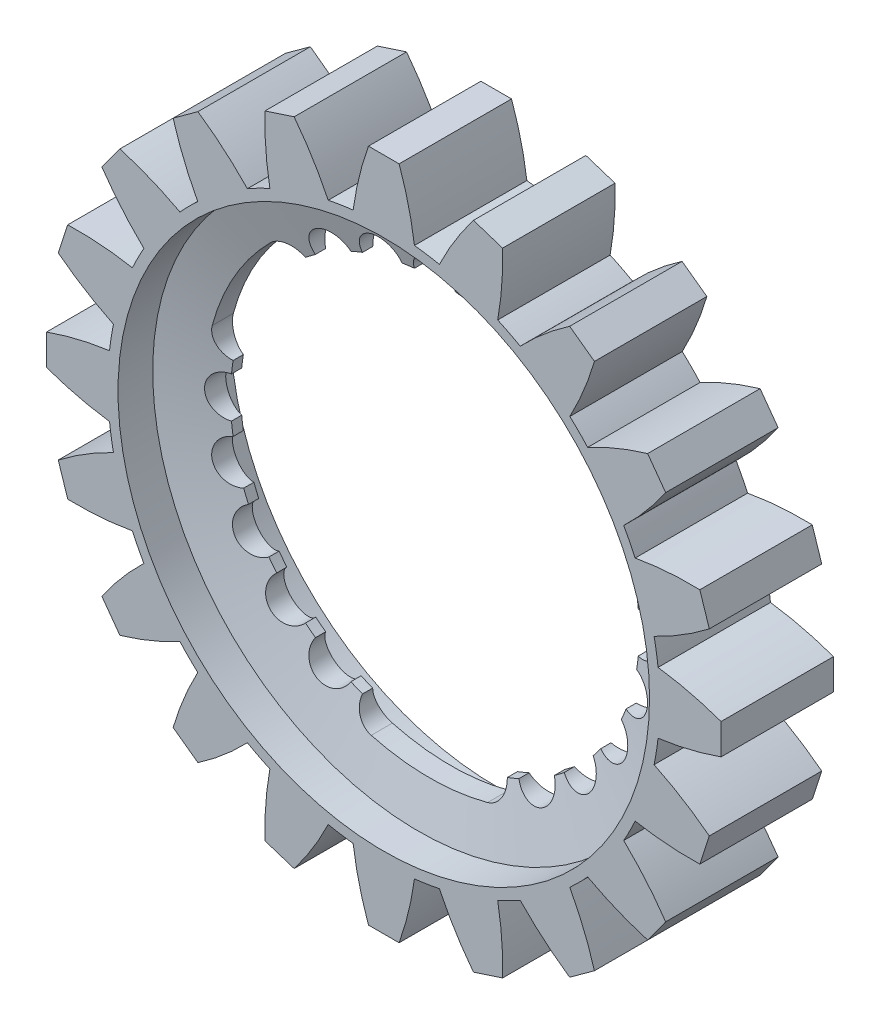
SolidWorks part; units mm, degrees
ref_plane "前视基准面" through (0, 0, 0) normal (0, 0, 1) x (1, 0, 0)
ref_plane "上视基准面" through (0, 0, 0) normal (0, 1, 0) x (1, 0, 0)
ref_plane "右视基准面" through (0, 0, 0) normal (1, 0, 0) x (0, 0, -1)
sketch "草图1" plane through (0, 0, 0) normal (0, 0, 1) x (1, 0, 0)
  circle A0 centre (0, 0) radius 13.5
extrude "凸台-拉伸1" add sketch "草图1" along normal blind 5.5
sketch "草图2" plane through (0, 0, 5.5) normal (0, 0, 1) x (1, 0, 0)
  circle A0 centre (0, 0) radius 10
extrude "切除-拉伸1" cut sketch "草图2" against normal through all
sketch "草图3" plane through (0, 0, 5.5) normal (0, 0, 1) x (1, 0, 0)
  circle A0 centre (0, 0) radius 13
extrude "切除-拉伸2" cut sketch "草图3" against normal blind 1.5
sketch "草图4" plane through (0, 0, 0) normal (0, 0, -1) x (-1, 0, 0)
  circle A0 centre (0, 0) radius 13
extrude "切除-拉伸3" cut sketch "草图4" against normal blind 1.5
chamfer "倒角1" distance 1 angle 75 2 edges at (-10, 0, 1.5) (10, 0, 4) first distance on face at (10, 0, 4)
sketch "草图5" plane through (0, 0, 5.5) normal (0, 0, 1) x (1, 0, 0)
  arc A0 (-1.6105, 9.8695) -> (-3.54, 9.3525) centre (0, 0) ccw
  arc A1 (-4.1101, 9.1163) -> (-5.8399, 8.1176) centre (-5, 8.6603) ccw
  arc A2 (-1.6105, 9.8695) -> (-3.54, 9.3525) centre (-2.5882, 9.6593) ccw
  arc A3 (0.9987, 9.95) -> (-0.9987, 9.95) centre (0, 10) ccw
  arc A4 (3.54, 9.3525) -> (1.6105, 9.8695) centre (2.5882, 9.6593) ccw
  arc A5 (5.8399, 8.1176) -> (4.1101, 9.1163) centre (5, 8.6603) ccw
  arc A6 (-6.3295, 7.7419) -> (-7.7782, 7.7782) centre (-7.0711, 7.0711) ccw
  arc A7 (7.7782, 7.7782) -> (6.3295, 7.7419) centre (7.0711, 7.0711) ccw
  arc A8 (-4.1101, 9.1163) -> (-5.8399, 8.1176) centre (0, 0) ccw
  arc A9 (-6.3295, 7.7419) -> (-9.8695, 1.6105) centre (0, 0) ccw
  arc A10 (0.9987, 9.95) -> (-0.9987, 9.95) centre (0, 0) ccw
  arc A11 (3.54, 9.3525) -> (1.6105, 9.8695) centre (0, 0) ccw
  arc A12 (5.8399, 8.1176) -> (4.1101, 9.1163) centre (0, 0) ccw
  arc A13 (-9.95, 0.9987) -> (-9.95, -0.9987) centre (-10, 0) ccw
  arc A14 (-9.8695, -1.6105) -> (-9.3525, -3.54) centre (-9.6593, -2.5882) ccw
  arc A15 (-9.1163, -4.1101) -> (-8.1176, -5.8399) centre (-8.6603, -5) ccw
  arc A16 (-7.7419, -6.3295) -> (-6.3295, -7.7419) centre (-7.0711, -7.0711) ccw
  arc A17 (-5.8399, -8.1176) -> (-4.1101, -9.1163) centre (-5, -8.6603) ccw
  arc A18 (-3.54, -9.3525) -> (-2.847, -10.6252) centre (-2.5882, -9.6593) ccw
  arc A19 (-9.8695, -1.6105) -> (-9.3525, -3.54) centre (0, 0) ccw
  arc A20 (-9.1163, -4.1101) -> (-8.1176, -5.8399) centre (0, 0) ccw
  arc A21 (-7.7419, -6.3295) -> (-6.3295, -7.7419) centre (0, 0) ccw
  arc A22 (-5.8399, -8.1176) -> (-4.1101, -9.1163) centre (0, 0) ccw
  arc A23 (7.7419, -6.3295) -> (6.3295, -7.7419) centre (0, 0) cw
  arc A24 (9.1163, -4.1101) -> (8.1176, -5.8399) centre (0, 0) cw
  arc A25 (9.8695, -1.6105) -> (9.3525, -3.54) centre (0, 0) cw
  arc A26 (3.54, -9.3525) -> (2.847, -10.6252) centre (2.5882, -9.6593) cw
  arc A27 (5.8399, -8.1176) -> (4.1101, -9.1163) centre (5, -8.6603) cw
  arc A28 (7.7419, -6.3295) -> (6.3295, -7.7419) centre (7.0711, -7.0711) cw
  arc A29 (9.1163, -4.1101) -> (8.1176, -5.8399) centre (8.6603, -5) cw
  arc A30 (9.8695, -1.6105) -> (9.3525, -3.54) centre (9.6593, -2.5882) cw
  arc A31 (9.95, 0.9987) -> (9.95, -0.9987) centre (10, 0) cw
  arc A32 (4.1101, -9.1163) -> (5.8399, -8.1176) centre (0, 0) ccw
  arc A36 (9.95, -0.9987) -> (9.95, 0.9987) centre (0, 0) ccw
  arc A37 (10.6252, 2.847) -> (7.7782, 7.7782) centre (0, 0) ccw
  arc A38 (9.8695, 1.6105) -> (10.6252, 2.847) centre (9.6593, 2.5882) ccw
  arc A39 (-10.6252, 2.847) -> (-9.8695, 1.6105) centre (-9.6593, 2.5882) ccw
  arc A40 (9.8695, 1.6105) -> (6.3295, 7.7419) centre (0, 0) ccw
  arc A41 (-7.7782, 7.7782) -> (-10.6252, 2.847) centre (0, 0) ccw
  arc A42 (-2.847, -10.6252) -> (2.847, -10.6252) centre (0, 0) ccw
  arc A43 (-9.95, 0.9987) -> (-9.95, -0.9987) centre (0, 0) ccw
  arc A44 (-3.54, -9.3525) -> (3.54, -9.3525) centre (0, 0) ccw
extrude "切除-拉伸4" cut sketch "草图5" against normal through all
sketch "草图6" plane through (0, 0, 5.5) normal (0, 0, 1) x (1, 0, 0)
  line L0 (5.8121, 15.4607) -> (4.3855, 15.9242)
  line L1 (10.3052, 12.9079) -> (9.0917, 13.7896)
  line L2 (0.75, 16.5) -> (-0.75, 16.5)
  line L3 (13.7896, 9.0917) -> (12.9079, 10.3052)
  line L4 (15.9242, 4.3855) -> (15.4607, 5.8121)
  line L5 (16.5, -0.75) -> (16.5, 0.75)
  line L6 (15.4607, -5.8121) -> (15.9242, -4.3855)
  line L7 (12.9079, -10.3052) -> (13.7896, -9.0917)
  line L8 (9.0917, -13.7896) -> (10.3052, -12.9079)
  line L9 (4.3855, -15.9242) -> (5.8121, -15.4607)
  line L10 (-0.75, -16.5) -> (0.75, -16.5)
  line L11 (-5.8121, -15.4607) -> (-4.3855, -15.9242)
  line L12 (-10.3052, -12.9079) -> (-9.0917, -13.7896)
  line L13 (-13.7896, -9.0917) -> (-12.9079, -10.3052)
  line L14 (-15.9242, -4.3855) -> (-15.4607, -5.8121)
  line L15 (-16.5, 0.75) -> (-16.5, -0.75)
  line L16 (-15.4607, 5.8121) -> (-15.9242, 4.3855)
  line L17 (-12.9079, 10.3052) -> (-13.7896, 9.0917)
  line L18 (-9.0917, 13.7896) -> (-10.3052, 12.9079)
  line L19 (-4.3855, 15.9242) -> (-5.8121, 15.4607)
  arc A0 (1.5, 13.4164) -> (-1.5, 13.4164) centre (0, 0) ccw
  arc A1 (-0.75, 16.5) -> (-1.5, 13.4164) centre (13.6132, 11.3735) ccw
  arc A2 (0.75, 16.5) -> (1.5, 13.4164) centre (-13.6132, 11.3735) cw
  arc A3 (5.5725, 12.2962) -> (2.7193, 13.2233) centre (0, 0) ccw
  arc A4 (4.3855, 15.9242) -> (2.7193, 13.2233) centre (16.4616, 6.6101) ccw
  arc A5 (5.8121, 15.4607) -> (5.5725, 12.2962) centre (-9.4324, 15.0236) cw
  arc A6 (9.0995, 9.9724) -> (6.6724, 11.7358) centre (0, 0) ccw
  arc A7 (9.0917, 13.7896) -> (6.6724, 11.7358) centre (17.6985, 1.1997) ccw
  arc A8 (10.3052, 12.9079) -> (9.0995, 9.9724) centre (-4.3282, 17.203) cw
  arc A9 (11.7358, 6.6724) -> (9.9724, 9.0995) centre (0, 0) ccw
  arc A10 (12.9079, 10.3052) -> (9.9724, 9.0995) centre (17.203, -4.3282) ccw
  arc A11 (13.7896, 9.0917) -> (11.7358, 6.6724) centre (1.1997, 17.6985) cw
  arc A12 (13.2233, 2.7193) -> (12.2962, 5.5725) centre (0, 0) ccw
  arc A13 (15.4607, 5.8121) -> (12.2962, 5.5725) centre (15.0236, -9.4324) ccw
  arc A14 (15.9242, 4.3855) -> (13.2233, 2.7193) centre (6.6101, 16.4616) cw
  arc A15 (13.4164, -1.5) -> (13.4164, 1.5) centre (0, 0) ccw
  arc A16 (16.5, 0.75) -> (13.4164, 1.5) centre (11.3735, -13.6132) ccw
  arc A17 (16.5, -0.75) -> (13.4164, -1.5) centre (11.3735, 13.6132) cw
  arc A18 (12.2962, -5.5725) -> (13.2233, -2.7193) centre (0, 0) ccw
  arc A19 (15.9242, -4.3855) -> (13.2233, -2.7193) centre (6.6101, -16.4616) ccw
  arc A20 (15.4607, -5.8121) -> (12.2962, -5.5725) centre (15.0236, 9.4324) cw
  arc A21 (9.9724, -9.0995) -> (11.7358, -6.6724) centre (0, 0) ccw
  arc A22 (13.7896, -9.0917) -> (11.7358, -6.6724) centre (1.1997, -17.6985) ccw
  arc A23 (12.9079, -10.3052) -> (9.9724, -9.0995) centre (17.203, 4.3282) cw
  arc A24 (6.6724, -11.7358) -> (9.0995, -9.9724) centre (0, 0) ccw
  arc A25 (10.3052, -12.9079) -> (9.0995, -9.9724) centre (-4.3282, -17.203) ccw
  arc A26 (9.0917, -13.7896) -> (6.6724, -11.7358) centre (17.6985, -1.1997) cw
  arc A27 (2.7193, -13.2233) -> (5.5725, -12.2962) centre (0, 0) ccw
  arc A28 (5.8121, -15.4607) -> (5.5725, -12.2962) centre (-9.4324, -15.0236) ccw
  arc A29 (4.3855, -15.9242) -> (2.7193, -13.2233) centre (16.4616, -6.6101) cw
  arc A30 (-1.5, -13.4164) -> (1.5, -13.4164) centre (0, 0) ccw
  arc A31 (0.75, -16.5) -> (1.5, -13.4164) centre (-13.6132, -11.3735) ccw
  arc A32 (-0.75, -16.5) -> (-1.5, -13.4164) centre (13.6132, -11.3735) cw
  arc A33 (-5.5725, -12.2962) -> (-2.7193, -13.2233) centre (0, 0) ccw
  arc A34 (-4.3855, -15.9242) -> (-2.7193, -13.2233) centre (-16.4616, -6.6101) ccw
  arc A35 (-5.8121, -15.4607) -> (-5.5725, -12.2962) centre (9.4324, -15.0236) cw
  arc A36 (-9.0995, -9.9724) -> (-6.6724, -11.7358) centre (0, 0) ccw
  arc A37 (-9.0917, -13.7896) -> (-6.6724, -11.7358) centre (-17.6985, -1.1997) ccw
  arc A38 (-10.3052, -12.9079) -> (-9.0995, -9.9724) centre (4.3282, -17.203) cw
  arc A39 (-11.7358, -6.6724) -> (-9.9724, -9.0995) centre (0, 0) ccw
  arc A40 (-12.9079, -10.3052) -> (-9.9724, -9.0995) centre (-17.203, 4.3282) ccw
  arc A41 (-13.7896, -9.0917) -> (-11.7358, -6.6724) centre (-1.1997, -17.6985) cw
  arc A42 (-13.2233, -2.7193) -> (-12.2962, -5.5725) centre (0, 0) ccw
  arc A43 (-15.4607, -5.8121) -> (-12.2962, -5.5725) centre (-15.0236, 9.4324) ccw
  arc A44 (-15.9242, -4.3855) -> (-13.2233, -2.7193) centre (-6.6101, -16.4616) cw
  arc A45 (-13.4164, 1.5) -> (-13.4164, -1.5) centre (0, 0) ccw
  arc A46 (-16.5, -0.75) -> (-13.4164, -1.5) centre (-11.3735, 13.6132) ccw
  arc A47 (-16.5, 0.75) -> (-13.4164, 1.5) centre (-11.3735, -13.6132) cw
  arc A48 (-12.2962, 5.5725) -> (-13.2233, 2.7193) centre (0, 0) ccw
  arc A49 (-15.9242, 4.3855) -> (-13.2233, 2.7193) centre (-6.6101, 16.4616) ccw
  arc A50 (-15.4607, 5.8121) -> (-12.2962, 5.5725) centre (-15.0236, -9.4324) cw
  arc A51 (-9.9724, 9.0995) -> (-11.7358, 6.6724) centre (0, 0) ccw
  arc A52 (-13.7896, 9.0917) -> (-11.7358, 6.6724) centre (-1.1997, 17.6985) ccw
  arc A53 (-12.9079, 10.3052) -> (-9.9724, 9.0995) centre (-17.203, -4.3282) cw
  arc A54 (-6.6724, 11.7358) -> (-9.0995, 9.9724) centre (0, 0) ccw
  arc A55 (-10.3052, 12.9079) -> (-9.0995, 9.9724) centre (4.3282, 17.203) ccw
  arc A56 (-9.0917, 13.7896) -> (-6.6724, 11.7358) centre (-17.6985, 1.1997) cw
  arc A57 (-2.7193, 13.2233) -> (-5.5725, 12.2962) centre (0, 0) ccw
  arc A58 (-5.8121, 15.4607) -> (-5.5725, 12.2962) centre (9.4324, 15.0236) ccw
  arc A59 (-4.3855, 15.9242) -> (-2.7193, 13.2233) centre (-16.4616, 6.6101) cw
  point P125 (0, 0)
  dimension "D1" = 20
extrude "凸台-拉伸2" add sketch "草图6" against normal up to surface (5.5 mm away) up to face at (-13, 0, 0)
